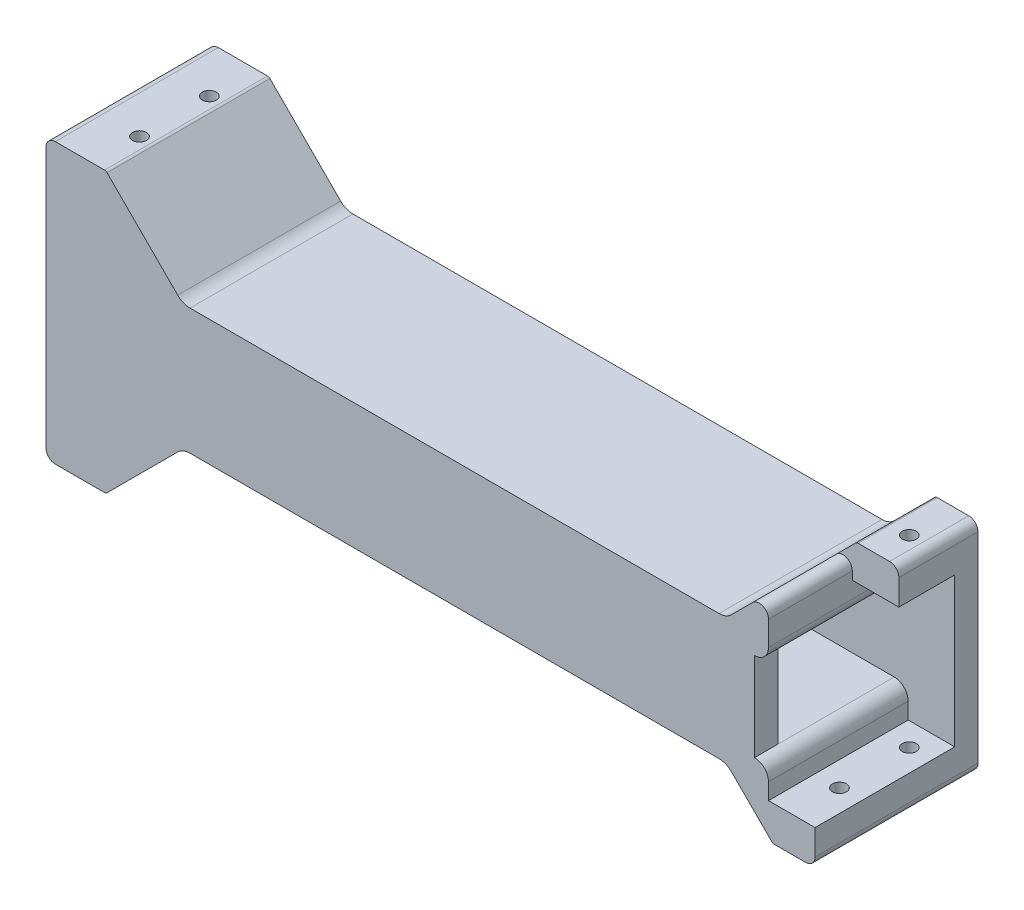
SolidWorks part; units mm, degrees
ref_plane "前视基准面" through (0, 0, 0) normal (0, 0, 1) x (1, 0, 0)
ref_plane "上视基准面" through (0, 0, 0) normal (0, 1, 0) x (1, 0, 0)
ref_plane "右视基准面" through (0, 0, 0) normal (1, 0, 0) x (0, 0, -1)
other "Configuration Table"
sketch "草图1" plane through (0, 0, 0) normal (0, 0, 1) x (1, 0, 0)
  line L43 (27.6425, 62.7843) -> (42.8324, 47.5944)
  line L44 (42.8324, 47.5944) -> (44.9537, 49.7157)
  line L45 (44.9537, 49.7157) -> (29.7639, 64.9056)
  line L46 (27.1217, 66) -> (-22.1169, 66)
  line L47 (-22.1169, 66) -> (-22.1169, 63)
  line L48 (-22.1169, 63) -> (27.1217, 63)
  line L49 (27.1217, 3) -> (-22.1169, 3)
  line L50 (-22.1169, 3) -> (-22.1169, 0)
  line L51 (-22.1169, 0) -> (27.1217, 0)
  line L52 (29.7639, 1.0944) -> (44.9537, 16.2843)
  line L53 (44.9537, 16.2843) -> (42.8324, 18.4056)
  line L54 (42.8324, 18.4056) -> (27.6425, 3.2157)
  line L55 (159.1217, 49.5) -> (45.4745, 49.5)
  line L56 (45.4745, 49.5) -> (45.4745, 46.5)
  line L57 (45.4745, 46.5) -> (159.1217, 46.5)
  line L58 (168.3324, 58.4056) -> (159.6425, 49.7157)
  line L59 (161.7639, 47.5944) -> (170.4537, 56.2843)
  line L60 (170.9745, 56.5) -> (183.3346, 56.5)
  line L61 (183.3346, 56.5) -> (183.3346, 59.5)
  line L62 (183.3346, 59.5) -> (170.9745, 59.5)
  line L63 (170.9745, 6.5) -> (183.3346, 6.5)
  line L64 (183.3346, 6.5) -> (183.3346, 9.5)
  line L65 (183.3346, 9.5) -> (170.9745, 9.5)
  line L66 (159.1217, 19.5) -> (45.4745, 19.5)
  line L67 (45.4745, 19.5) -> (45.4745, 16.5)
  line L68 (45.4745, 16.5) -> (159.1217, 16.5)
  line L69 (170.4537, 9.7157) -> (161.7639, 18.4056)
  line L70 (159.6425, 16.2843) -> (168.3324, 7.5944)
  line L71 (14.5441, 63) -> (14.5441, 3)
  line L72 (179.7384, 56.5) -> (179.7384, 9.5)
  line L79 (168.3324, 7.5944) -> (170.4537, 9.7157)
  line L80 (170.4537, 9.7157) -> (161.7639, 18.4056)
  line L81 (161.7639, 18.4056) -> (159.6425, 16.2843)
  line L82 (159.6425, 16.2843) -> (168.3324, 7.5944)
  arc A14 (27.6425, 62.7843) -> (27.1217, 63) centre (27.1217, 62.2634) ccw
  arc A15 (29.7639, 64.9056) -> (27.1217, 66) centre (27.1217, 62.2634) ccw
  arc A16 (27.1217, 0) -> (29.7639, 1.0944) centre (27.1217, 3.7366) ccw
  arc A17 (27.1217, 3) -> (27.6425, 3.2157) centre (27.1217, 3.7366) ccw
  arc A18 (159.1217, 46.5) -> (161.7639, 47.5944) centre (159.1217, 50.2366) ccw
  arc A19 (159.1217, 49.5) -> (159.6425, 49.7157) centre (159.1217, 50.2366) ccw
  arc A20 (170.9745, 56.5) -> (170.4537, 56.2843) centre (170.9745, 55.7634) ccw
  arc A21 (170.9745, 59.5) -> (168.3324, 58.4056) centre (170.9745, 55.7634) ccw
  arc A22 (168.3324, 7.5944) -> (170.9745, 6.5) centre (170.9745, 10.2366) ccw
  arc A23 (170.4537, 9.7157) -> (170.9745, 9.5) centre (170.9745, 10.2366) ccw
  arc A24 (159.6425, 16.2843) -> (159.1217, 16.5) centre (159.1217, 15.7634) ccw
  arc A25 (161.7639, 18.4056) -> (159.1217, 19.5) centre (159.1217, 15.7634) ccw
  arc A26 (45.4745, 19.5) -> (42.8324, 18.4056) centre (45.4745, 15.7634) ccw
  arc A27 (45.4745, 16.5) -> (44.9537, 16.2843) centre (45.4745, 15.7634) ccw
  arc A28 (45.4745, 49.5) -> (44.9537, 49.7157) centre (45.4745, 50.2366) cw
  arc A29 (45.4745, 46.5) -> (42.8324, 47.5944) centre (45.4745, 50.2366) cw
extrude "凸台-拉伸1" add sketch "草图1" along normal blind 35 contours L57 A29 L43 A14 L48 L71 L49 A17 L54 A26 L66 A25 L69 A23 L65 L72 L60 A20 L59 A18 region at (91.8705, 33, 0)
sketch "草图3" plane through (14.5441, 0, 0) normal (-1, 0, 0) x (0, 0, 1)
  line L0 (35, 46.5) -> (0, 46.5) construction
  line L1 (35, 19.5) -> (0, 19.5) construction
  line L2 (35, 46.5) -> (0, 46.5) construction
  line L3 (35, 19.5) -> (0, 19.5) construction
  line L4 (0, 46.5) -> (35, 19.5) construction
  line L5 (35, 46.5) -> (0, 19.5) construction
  line L6 (35, 63) -> (35, 3) construction
  line L7 (5, 42.5) -> (30, 42.5)
  line L8 (5, 42.5) -> (5, 23.5)
  line L9 (5, 23.5) -> (30, 23.5)
  line L10 (30, 42.5) -> (30, 23.5)
  line L11 (5, 42.5) -> (30, 23.5) construction
  line L12 (5, 23.5) -> (30, 42.5) construction
  point P4 (17.5, 33)
  dimension "D1" = 5
  dimension "D2" = 4
extrude "切除-拉伸1" cut sketch "草图3" against normal through all
sketch "草图4" plane through (14.5441, 0, 0) normal (-1, 0, 0) x (0, 0, 1)
  line L18 (0, 63) -> (0, 3)
  line L19 (0, 3) -> (35, 3)
  line L20 (35, 3) -> (35, 63)
  line L39 (35, 63) -> (0, 63)
  line L40 (0, 63) -> (0, 3)
  line L41 (0, 3) -> (35, 3)
  line L42 (35, 3) -> (35, 63)
  line L43 (35, 63) -> (0, 63)
  line L44 (5, 55) -> (30, 55)
  line L45 (5, 11) -> (30, 11)
  line L48 (5, 58) -> (5, 8)
  line L49 (5, 8) -> (30, 8)
  line L50 (30, 8) -> (30, 58)
  line L51 (30, 58) -> (5, 58)
  line L52 (5, 58) -> (5, 8)
  line L53 (5, 8) -> (30, 8)
  line L54 (30, 8) -> (30, 58)
  line L55 (30, 58) -> (5, 58)
  line M5 (5, 42.5) -> (30, 42.5)
  line M7 (30, 23.5) -> (5, 23.5)
  dimension "D3" = 3
  dimension "D4" = 3
  dimension "D1" = 0
  dimension "D2" = 5
extrude "切除-拉伸2" cut sketch "草图4" against normal blind 13.5 contours M5 | M7 region at (14.5441, 48.75, 17.5) region at (14.5441, 17.25, 17.5)
sketch "草图5" plane through (179.7384, 0, 0) normal (1, 0, 0) x (0, 0, -1)
  line L0 (-35, 56.5) -> (0, 9.5) construction
  line L1 (-35, 9.5) -> (0, 56.5) construction
  line L4 (-30, 49) -> (-5, 49)
  line L5 (0, 9.5) -> (0, 56.5)
  line L7 (0, 56.5) -> (-35, 56.5)
  line L16 (-35, 56.5) -> (-35, 9.5)
  line L18 (-35, 9.5) -> (0, 9.5)
  line L19 (0, 9.5) -> (0, 56.5) construction
  line L20 (0, 56.5) -> (-35, 56.5) construction
  line L23 (-35, 56.5) -> (-35, 9.5) construction
  line L24 (-35, 9.5) -> (0, 9.5) construction
  line L25 (-30, 49) -> (-30, 17)
  line L26 (-30, 17) -> (-5, 17)
  line L27 (-5, 49) -> (-5, 17)
  line L28 (-30, 49) -> (-5, 17) construction
  line L29 (-30, 17) -> (-5, 49) construction
  point P2 (-17.5, 33)
  dimension "D2" = 25
  dimension "D3" = 32
  dimension "D1" = 0
extrude "切除-拉伸3" cut sketch "草图5" against normal blind 10
fillet "圆角1" radius 3 4 edges at (169.7384, 23.5, 17.5) (169.7384, 42.5, 17.5) (28.0441, 42.5, 17.5) (28.0441, 23.5, 17.5)
fillet "圆角2" radius 2 4 edges at (179.7384, 56.5, 17.5) (179.7384, 9.5, 17.5) (14.5441, 63, 17.5) (14.5441, 3, 17.5)
sketch "草图6" plane through (0, 55, 0) normal (0, -1, 0) x (1, 0, 0)
  circle A0 centre (24.6217, 25) radius 1.5 construction
  circle A1 centre (24.6217, 25) radius 1.5
  circle A2 centre (24.6217, 10) radius 1.5 construction
  circle A3 centre (24.6217, 10) radius 1.5
extrude "切除-拉伸4" cut sketch "草图6" against normal through all and the other way through all
sketch "草图7" plane through (0, 49, 0) normal (0, -1, 0) x (1, 0, 0)
  circle A0 centre (174.9745, 25) radius 1.5 construction
  circle A1 centre (174.9745, 10) radius 1.5 construction
  circle A2 centre (174.9745, 25) radius 1.5
  circle A3 centre (174.9745, 10) radius 1.5
extrude "切除-拉伸5" cut sketch "草图7" against normal through all and the other way through all
sketch "草图8" plane through (0, 0, 5) normal (0, 0, 1) x (1, 0, 0)
  line L0 (28.0441, 45.5) -> (28.0441, 20.5)
  line L1 (169.7384, 45.5) -> (169.7384, 20.5)
  line L12 (179.7384, 17) -> (179.7384, 49)
  line L13 (179.7384, 49) -> (169.7384, 49)
  line L14 (169.7384, 49) -> (169.7384, 45.5)
  line L15 (166.7384, 42.5) -> (31.0441, 42.5)
  line L16 (28.0441, 45.5) -> (28.0441, 55)
  line L17 (28.0441, 55) -> (14.5441, 55)
  line L18 (14.5441, 55) -> (14.5441, 11)
  line L19 (14.5441, 11) -> (28.0441, 11)
  line L20 (28.0441, 11) -> (28.0441, 20.5)
  line L21 (31.0441, 23.5) -> (166.7384, 23.5)
  line L22 (169.7384, 20.5) -> (169.7384, 17)
  line L23 (169.7384, 17) -> (179.7384, 17)
  line L24 (179.7384, 17) -> (179.7384, 49)
  line L25 (179.7384, 49) -> (169.7384, 49)
  line L26 (169.7384, 49) -> (169.7384, 45.5)
  line L27 (166.7384, 42.5) -> (31.0441, 42.5)
  line L28 (28.0441, 45.5) -> (28.0441, 55)
  line L29 (28.0441, 55) -> (14.5441, 55)
  line L30 (14.5441, 55) -> (14.5441, 11)
  line L31 (14.5441, 11) -> (28.0441, 11)
  line L32 (28.0441, 11) -> (28.0441, 20.5)
  line L33 (31.0441, 23.5) -> (166.7384, 23.5)
  line L34 (169.7384, 20.5) -> (169.7384, 17)
  line L35 (169.7384, 17) -> (179.7384, 17)
  arc A4 (166.7384, 42.5) -> (169.7384, 45.5) centre (166.7384, 45.5) ccw
  arc A5 (28.0441, 45.5) -> (31.0441, 42.5) centre (31.0441, 45.5) ccw
  arc A6 (31.0441, 23.5) -> (28.0441, 20.5) centre (31.0441, 20.5) ccw
  arc A7 (169.7384, 20.5) -> (166.7384, 23.5) centre (166.7384, 20.5) ccw
  arc A8 (166.7384, 42.5) -> (169.7384, 45.5) centre (166.7384, 45.5) ccw
  arc A9 (28.0441, 45.5) -> (31.0441, 42.5) centre (31.0441, 45.5) ccw
  arc A10 (31.0441, 23.5) -> (28.0441, 20.5) centre (31.0441, 20.5) ccw
  arc A11 (169.7384, 20.5) -> (166.7384, 23.5) centre (166.7384, 20.5) ccw
  line M17 (179.7384, 17) -> (179.7384, 49)
  line M18 (179.7384, 49) -> (169.7384, 49)
  line M19 (169.7384, 49) -> (169.7384, 45.5)
  arc M20 (169.7384, 45.5) -> (166.7384, 42.5) centre (166.7384, 45.5) cw
  line M23 (28.0441, 45.5) -> (28.0441, 55)
  line M24 (28.0441, 55) -> (14.5441, 55)
  line M25 (14.5441, 55) -> (14.5441, 11)
  line M26 (14.5441, 11) -> (28.0441, 11)
  line M27 (28.0441, 11) -> (28.0441, 20.5)
  arc M30 (166.7384, 23.5) -> (169.7384, 20.5) centre (166.7384, 20.5) cw
  line M31 (169.7384, 20.5) -> (169.7384, 17)
  line M32 (169.7384, 17) -> (179.7384, 17)
  dimension "D1" = 0
extrude "切除-拉伸6" cut sketch "草图8" against normal through all contours M20 M30 M31 M32 M17 M18 M19 | L0 M23 M24 M25 M26 M27 region at (21.2941, 33, 5) region at (174.7384, 33, 5)
sketch "草图9" plane through (0, 0, 30) normal (0, 0, -1) x (-1, 0, 0)
  line L0 (-179.7384, 49) -> (-179.7384, 17)
  line L20 (-179.7384, 54.5) -> (-179.7384, 49)
  line L21 (-179.7384, 49) -> (-169.7384, 49)
  line L22 (-169.7384, 49) -> (-169.7384, 17)
  line L23 (-169.7384, 17) -> (-179.7384, 17)
  line L24 (-179.7384, 17) -> (-179.7384, 11.5)
  line L25 (-177.7384, 9.5) -> (-170.9745, 9.5)
  line L26 (-170.4537, 9.7157) -> (-161.7639, 18.4056)
  line L27 (-159.1217, 19.5) -> (-45.4745, 19.5)
  line L28 (-42.8324, 18.4056) -> (-27.6425, 3.2157)
  line L29 (-27.1217, 3) -> (-16.5441, 3)
  line L30 (-14.5441, 5) -> (-14.5441, 11)
  line L31 (-14.5441, 11) -> (-28.0441, 11)
  line L32 (-28.0441, 11) -> (-28.0441, 55)
  line L33 (-28.0441, 55) -> (-14.5441, 55)
  line L34 (-14.5441, 55) -> (-14.5441, 61)
  line L35 (-16.5441, 63) -> (-27.1217, 63)
  line L36 (-27.6425, 62.7843) -> (-42.8324, 47.5944)
  line L37 (-45.4745, 46.5) -> (-159.1217, 46.5)
  line L38 (-161.7639, 47.5944) -> (-170.4537, 56.2843)
  line L39 (-170.9745, 56.5) -> (-177.7384, 56.5)
  line L40 (-179.7384, 54.5) -> (-179.7384, 49)
  line L41 (-179.7384, 49) -> (-169.7384, 49)
  line L42 (-169.7384, 49) -> (-169.7384, 17)
  line L43 (-169.7384, 17) -> (-179.7384, 17)
  line L44 (-179.7384, 17) -> (-179.7384, 11.5)
  line L45 (-177.7384, 9.5) -> (-170.9745, 9.5)
  line L46 (-170.4537, 9.7157) -> (-161.7639, 18.4056)
  line L47 (-159.1217, 19.5) -> (-45.4745, 19.5)
  line L48 (-42.8324, 18.4056) -> (-27.6425, 3.2157)
  line L49 (-27.1217, 3) -> (-16.5441, 3)
  line L50 (-14.5441, 5) -> (-14.5441, 11)
  line L51 (-14.5441, 11) -> (-28.0441, 11)
  line L52 (-28.0441, 11) -> (-28.0441, 55)
  line L53 (-28.0441, 55) -> (-14.5441, 55)
  line L54 (-14.5441, 55) -> (-14.5441, 61)
  line L55 (-16.5441, 63) -> (-27.1217, 63)
  line L56 (-27.6425, 62.7843) -> (-42.8324, 47.5944)
  line L57 (-45.4745, 46.5) -> (-159.1217, 46.5)
  line L58 (-161.7639, 47.5944) -> (-170.4537, 56.2843)
  line L59 (-170.9745, 56.5) -> (-177.7384, 56.5)
  arc A12 (-179.7384, 11.5) -> (-177.7384, 9.5) centre (-177.7384, 11.5) ccw
  arc A13 (-170.9745, 9.5) -> (-170.4537, 9.7157) centre (-170.9745, 10.2366) ccw
  arc A14 (-159.1217, 19.5) -> (-161.7639, 18.4056) centre (-159.1217, 15.7634) ccw
  arc A15 (-42.8324, 18.4056) -> (-45.4745, 19.5) centre (-45.4745, 15.7634) ccw
  arc A16 (-27.6425, 3.2157) -> (-27.1217, 3) centre (-27.1217, 3.7366) ccw
  arc A17 (-16.5441, 3) -> (-14.5441, 5) centre (-16.5441, 5) ccw
  arc A18 (-14.5441, 61) -> (-16.5441, 63) centre (-16.5441, 61) ccw
  arc A19 (-27.1217, 63) -> (-27.6425, 62.7843) centre (-27.1217, 62.2634) ccw
  arc A20 (-45.4745, 46.5) -> (-42.8324, 47.5944) centre (-45.4745, 50.2366) ccw
  arc A21 (-161.7639, 47.5944) -> (-159.1217, 46.5) centre (-159.1217, 50.2366) ccw
  arc A22 (-170.4537, 56.2843) -> (-170.9745, 56.5) centre (-170.9745, 55.7634) ccw
  arc A23 (-177.7384, 56.5) -> (-179.7384, 54.5) centre (-177.7384, 54.5) ccw
  arc A24 (-179.7384, 11.5) -> (-177.7384, 9.5) centre (-177.7384, 11.5) ccw
  arc A25 (-170.9745, 9.5) -> (-170.4537, 9.7157) centre (-170.9745, 10.2366) ccw
  arc A26 (-159.1217, 19.5) -> (-161.7639, 18.4056) centre (-159.1217, 15.7634) ccw
  arc A27 (-42.8324, 18.4056) -> (-45.4745, 19.5) centre (-45.4745, 15.7634) ccw
  arc A28 (-27.6425, 3.2157) -> (-27.1217, 3) centre (-27.1217, 3.7366) ccw
  arc A29 (-16.5441, 3) -> (-14.5441, 5) centre (-16.5441, 5) ccw
  arc A30 (-14.5441, 61) -> (-16.5441, 63) centre (-16.5441, 61) ccw
  arc A31 (-27.1217, 63) -> (-27.6425, 62.7843) centre (-27.1217, 62.2634) ccw
  arc A32 (-45.4745, 46.5) -> (-42.8324, 47.5944) centre (-45.4745, 50.2366) ccw
  arc A33 (-161.7639, 47.5944) -> (-159.1217, 46.5) centre (-159.1217, 50.2366) ccw
  arc A34 (-170.4537, 56.2843) -> (-170.9745, 56.5) centre (-170.9745, 55.7634) ccw
  arc A35 (-177.7384, 56.5) -> (-179.7384, 54.5) centre (-177.7384, 54.5) ccw
  line M33 (-179.7384, 49) -> (-179.7384, 17)
  line M34 (-179.7384, 17) -> (-169.7384, 17)
  line M35 (-169.7384, 17) -> (-169.7384, 20.5)
  line M47 (-169.7384, 45.5) -> (-169.7384, 49)
  line M48 (-169.7384, 49) -> (-179.7384, 49)
  dimension "D1" = 0
extrude "切除-拉伸7" cut sketch "草图9" against normal blind 10 contours L42 M47 M48 M33 M34 M35 region at (174.7384, 33, 30)
sketch "草图10" plane through (0, 0, 35) normal (0, 0, 1) x (1, 0, 0)
  line L0 (169.7384, 49) -> (169.7384, 55.569)
  line L16 (179.7384, 17) -> (169.7384, 17)
  line L17 (169.7384, 17) -> (169.7384, 49)
  line L18 (169.7384, 49) -> (179.7384, 49)
  line L19 (179.7384, 49) -> (179.7384, 54.5)
  line L20 (177.7384, 56.5) -> (170.9745, 56.5)
  line L21 (170.4537, 56.2843) -> (161.7639, 47.5944)
  line L22 (159.1217, 46.5) -> (45.4745, 46.5)
  line L23 (42.8324, 47.5944) -> (27.6425, 62.7843)
  line L24 (27.1217, 63) -> (16.5441, 63)
  line L25 (14.5441, 61) -> (14.5441, 5)
  line L26 (16.5441, 3) -> (27.1217, 3)
  line L27 (27.6425, 3.2157) -> (42.8324, 18.4056)
  line L28 (45.4745, 19.5) -> (159.1217, 19.5)
  line L29 (161.7639, 18.4056) -> (170.4537, 9.7157)
  line L30 (170.9745, 9.5) -> (177.7384, 9.5)
  line L31 (179.7384, 11.5) -> (179.7384, 17)
  line L32 (179.7384, 17) -> (169.7384, 17)
  line L33 (169.7384, 17) -> (169.7384, 49)
  line L34 (169.7384, 49) -> (179.7384, 49)
  line L35 (179.7384, 49) -> (179.7384, 54.5)
  line L36 (177.7384, 56.5) -> (170.9745, 56.5)
  line L37 (170.4537, 56.2843) -> (161.7639, 47.5944)
  line L38 (159.1217, 46.5) -> (45.4745, 46.5)
  line L39 (42.8324, 47.5944) -> (27.6425, 62.7843)
  line L40 (27.1217, 63) -> (16.5441, 63)
  line L41 (14.5441, 61) -> (14.5441, 5)
  line L42 (16.5441, 3) -> (27.1217, 3)
  line L43 (27.6425, 3.2157) -> (42.8324, 18.4056)
  line L44 (45.4745, 19.5) -> (159.1217, 19.5)
  line L45 (161.7639, 18.4056) -> (170.4537, 9.7157)
  line L46 (170.9745, 9.5) -> (177.7384, 9.5)
  line L47 (179.7384, 11.5) -> (179.7384, 17)
  arc A12 (179.7384, 54.5) -> (177.7384, 56.5) centre (177.7384, 54.5) ccw
  arc A13 (170.9745, 56.5) -> (170.4537, 56.2843) centre (170.9745, 55.7634) ccw
  arc A14 (159.1217, 46.5) -> (161.7639, 47.5944) centre (159.1217, 50.2366) ccw
  arc A15 (42.8324, 47.5944) -> (45.4745, 46.5) centre (45.4745, 50.2366) ccw
  arc A16 (27.6425, 62.7843) -> (27.1217, 63) centre (27.1217, 62.2634) ccw
  arc A17 (16.5441, 63) -> (14.5441, 61) centre (16.5441, 61) ccw
  arc A18 (14.5441, 5) -> (16.5441, 3) centre (16.5441, 5) ccw
  arc A19 (27.1217, 3) -> (27.6425, 3.2157) centre (27.1217, 3.7366) ccw
  arc A20 (45.4745, 19.5) -> (42.8324, 18.4056) centre (45.4745, 15.7634) ccw
  arc A21 (161.7639, 18.4056) -> (159.1217, 19.5) centre (159.1217, 15.7634) ccw
  arc A22 (170.4537, 9.7157) -> (170.9745, 9.5) centre (170.9745, 10.2366) ccw
  arc A23 (177.7384, 9.5) -> (179.7384, 11.5) centre (177.7384, 11.5) ccw
  arc A24 (179.7384, 54.5) -> (177.7384, 56.5) centre (177.7384, 54.5) ccw
  arc A25 (170.9745, 56.5) -> (170.4537, 56.2843) centre (170.9745, 55.7634) ccw
  arc A26 (159.1217, 46.5) -> (161.7639, 47.5944) centre (159.1217, 50.2366) ccw
  arc A27 (42.8324, 47.5944) -> (45.4745, 46.5) centre (45.4745, 50.2366) ccw
  arc A28 (27.6425, 62.7843) -> (27.1217, 63) centre (27.1217, 62.2634) ccw
  arc A29 (16.5441, 63) -> (14.5441, 61) centre (16.5441, 61) ccw
  arc A30 (14.5441, 5) -> (16.5441, 3) centre (16.5441, 5) ccw
  arc A31 (27.1217, 3) -> (27.6425, 3.2157) centre (27.1217, 3.7366) ccw
  arc A32 (45.4745, 19.5) -> (42.8324, 18.4056) centre (45.4745, 15.7634) ccw
  arc A33 (161.7639, 18.4056) -> (159.1217, 19.5) centre (159.1217, 15.7634) ccw
  arc A34 (170.4537, 9.7157) -> (170.9745, 9.5) centre (170.9745, 10.2366) ccw
  arc A35 (177.7384, 9.5) -> (179.7384, 11.5) centre (177.7384, 11.5) ccw
  line M31 (169.7384, 49) -> (179.7384, 49)
  line M32 (179.7384, 49) -> (179.7384, 54.5)
  arc M33 (179.7384, 54.5) -> (177.7384, 56.5) centre (177.7384, 54.5) ccw
  line M34 (177.7384, 56.5) -> (170.9745, 56.5)
  arc M35 (170.9745, 56.5) -> (170.4537, 56.2843) centre (170.9745, 55.7634) ccw
  line M36 (170.4537, 56.2843) -> (161.7639, 47.5944)
  dimension "D1" = 0
extrude "切除-拉伸8" cut sketch "草图10" against normal blind 18 contours L0 M31 M32 M33 M34 M35 M36 region at (174.7136, 52.6907, 35)
fillet "圆角3" radius 2 1 edges at (169.7384, 55.569, 26)
sketch "草图11" plane through (0, 0, 0) normal (0, 0, -1) x (-1, 0, 0)
  line L0 (-179.7384, 49) -> (-179.7384, 17)
  line L20 (-179.7384, 54.5) -> (-179.7384, 49)
  line L21 (-179.7384, 49) -> (-169.7384, 49)
  line L22 (-169.7384, 49) -> (-169.7384, 17)
  line L23 (-169.7384, 17) -> (-179.7384, 17)
  line L24 (-179.7384, 17) -> (-179.7384, 11.5)
  line L25 (-177.7384, 9.5) -> (-170.9745, 9.5)
  line L26 (-170.4537, 9.7157) -> (-161.7639, 18.4056)
  line L27 (-159.1217, 19.5) -> (-45.4745, 19.5)
  line L28 (-42.8324, 18.4056) -> (-27.6425, 3.2157)
  line L29 (-27.1217, 3) -> (-16.5441, 3)
  line L30 (-14.5441, 5) -> (-14.5441, 11)
  line L31 (-14.5441, 11) -> (-28.0441, 11)
  line L32 (-28.0441, 11) -> (-28.0441, 55)
  line L33 (-28.0441, 55) -> (-14.5441, 55)
  line L34 (-14.5441, 55) -> (-14.5441, 61)
  line L35 (-16.5441, 63) -> (-27.1217, 63)
  line L36 (-27.6425, 62.7843) -> (-42.8324, 47.5944)
  line L37 (-45.4745, 46.5) -> (-159.1217, 46.5)
  line L38 (-161.7639, 47.5944) -> (-170.4537, 56.2843)
  line L39 (-170.9745, 56.5) -> (-177.7384, 56.5)
  line L40 (-179.7384, 54.5) -> (-179.7384, 49)
  line L41 (-179.7384, 49) -> (-169.7384, 49)
  line L42 (-169.7384, 49) -> (-169.7384, 17)
  line L43 (-169.7384, 17) -> (-179.7384, 17)
  line L44 (-179.7384, 17) -> (-179.7384, 11.5)
  line L45 (-177.7384, 9.5) -> (-170.9745, 9.5)
  line L46 (-170.4537, 9.7157) -> (-161.7639, 18.4056)
  line L47 (-159.1217, 19.5) -> (-45.4745, 19.5)
  line L48 (-42.8324, 18.4056) -> (-27.6425, 3.2157)
  line L49 (-27.1217, 3) -> (-16.5441, 3)
  line L50 (-14.5441, 5) -> (-14.5441, 11)
  line L51 (-14.5441, 11) -> (-28.0441, 11)
  line L52 (-28.0441, 11) -> (-28.0441, 55)
  line L53 (-28.0441, 55) -> (-14.5441, 55)
  line L54 (-14.5441, 55) -> (-14.5441, 61)
  line L55 (-16.5441, 63) -> (-27.1217, 63)
  line L56 (-27.6425, 62.7843) -> (-42.8324, 47.5944)
  line L57 (-45.4745, 46.5) -> (-159.1217, 46.5)
  line L58 (-161.7639, 47.5944) -> (-170.4537, 56.2843)
  line L59 (-170.9745, 56.5) -> (-177.7384, 56.5)
  arc A12 (-179.7384, 11.5) -> (-177.7384, 9.5) centre (-177.7384, 11.5) ccw
  arc A13 (-170.9745, 9.5) -> (-170.4537, 9.7157) centre (-170.9745, 10.2366) ccw
  arc A14 (-159.1217, 19.5) -> (-161.7639, 18.4056) centre (-159.1217, 15.7634) ccw
  arc A15 (-42.8324, 18.4056) -> (-45.4745, 19.5) centre (-45.4745, 15.7634) ccw
  arc A16 (-27.6425, 3.2157) -> (-27.1217, 3) centre (-27.1217, 3.7366) ccw
  arc A17 (-16.5441, 3) -> (-14.5441, 5) centre (-16.5441, 5) ccw
  arc A18 (-14.5441, 61) -> (-16.5441, 63) centre (-16.5441, 61) ccw
  arc A19 (-27.1217, 63) -> (-27.6425, 62.7843) centre (-27.1217, 62.2634) ccw
  arc A20 (-45.4745, 46.5) -> (-42.8324, 47.5944) centre (-45.4745, 50.2366) ccw
  arc A21 (-161.7639, 47.5944) -> (-159.1217, 46.5) centre (-159.1217, 50.2366) ccw
  arc A22 (-170.4537, 56.2843) -> (-170.9745, 56.5) centre (-170.9745, 55.7634) ccw
  arc A23 (-177.7384, 56.5) -> (-179.7384, 54.5) centre (-177.7384, 54.5) ccw
  arc A24 (-179.7384, 11.5) -> (-177.7384, 9.5) centre (-177.7384, 11.5) ccw
  arc A25 (-170.9745, 9.5) -> (-170.4537, 9.7157) centre (-170.9745, 10.2366) ccw
  arc A26 (-159.1217, 19.5) -> (-161.7639, 18.4056) centre (-159.1217, 15.7634) ccw
  arc A27 (-42.8324, 18.4056) -> (-45.4745, 19.5) centre (-45.4745, 15.7634) ccw
  arc A28 (-27.6425, 3.2157) -> (-27.1217, 3) centre (-27.1217, 3.7366) ccw
  arc A29 (-16.5441, 3) -> (-14.5441, 5) centre (-16.5441, 5) ccw
  arc A30 (-14.5441, 61) -> (-16.5441, 63) centre (-16.5441, 61) ccw
  arc A31 (-27.1217, 63) -> (-27.6425, 62.7843) centre (-27.1217, 62.2634) ccw
  arc A32 (-45.4745, 46.5) -> (-42.8324, 47.5944) centre (-45.4745, 50.2366) ccw
  arc A33 (-161.7639, 47.5944) -> (-159.1217, 46.5) centre (-159.1217, 50.2366) ccw
  arc A34 (-170.4537, 56.2843) -> (-170.9745, 56.5) centre (-170.9745, 55.7634) ccw
  arc A35 (-177.7384, 56.5) -> (-179.7384, 54.5) centre (-177.7384, 54.5) ccw
  line M34 (-179.7384, 49) -> (-169.7384, 49)
  line M35 (-169.7384, 49) -> (-169.7384, 17)
  line M36 (-169.7384, 17) -> (-179.7384, 17)
  dimension "D1" = 0
extrude "凸台-拉伸2" add sketch "草图11" against normal blind 5 contours L0 M34 M36 M35 region at (174.7384, 33, 0)
sketch "草图12" plane through (0, 0, 30) normal (0, 0, -1) x (-1, 0, 0)
  line L0 (-166.7384, 42.5) -> (-166.7384, 23.5)
  line L8 (-169.7384, 45.5) -> (-169.7384, 20.5)
  line L9 (-166.7384, 23.5) -> (-31.0441, 23.5)
  line L10 (-28.0441, 20.5) -> (-28.0441, 11)
  line L11 (-28.0441, 11) -> (-14.5441, 11)
  line L12 (-14.5441, 11) -> (-14.5441, 55)
  line L13 (-14.5441, 55) -> (-28.0441, 55)
  line L14 (-28.0441, 55) -> (-28.0441, 45.5)
  line L15 (-31.0441, 42.5) -> (-166.7384, 42.5)
  line L16 (-169.7384, 45.5) -> (-169.7384, 20.5)
  line L17 (-166.7384, 23.5) -> (-31.0441, 23.5)
  line L18 (-28.0441, 20.5) -> (-28.0441, 11)
  line L19 (-28.0441, 11) -> (-14.5441, 11)
  line L20 (-14.5441, 11) -> (-14.5441, 55)
  line L21 (-14.5441, 55) -> (-28.0441, 55)
  line L22 (-28.0441, 55) -> (-28.0441, 45.5)
  line L23 (-31.0441, 42.5) -> (-166.7384, 42.5)
  arc A4 (-166.7384, 23.5) -> (-169.7384, 20.5) centre (-166.7384, 20.5) ccw
  arc A5 (-28.0441, 20.5) -> (-31.0441, 23.5) centre (-31.0441, 20.5) ccw
  arc A6 (-31.0441, 42.5) -> (-28.0441, 45.5) centre (-31.0441, 45.5) ccw
  arc A7 (-169.7384, 45.5) -> (-166.7384, 42.5) centre (-166.7384, 45.5) ccw
  arc A8 (-166.7384, 23.5) -> (-169.7384, 20.5) centre (-166.7384, 20.5) ccw
  arc A9 (-28.0441, 20.5) -> (-31.0441, 23.5) centre (-31.0441, 20.5) ccw
  arc A10 (-31.0441, 42.5) -> (-28.0441, 45.5) centre (-31.0441, 45.5) ccw
  arc A11 (-169.7384, 45.5) -> (-166.7384, 42.5) centre (-166.7384, 45.5) ccw
  dimension "D1" = 0
extrude "切除-拉伸10" cut sketch "草图12" against normal blind 5 contours L0 A6 L8 region at (168.2911, 33, 30)
